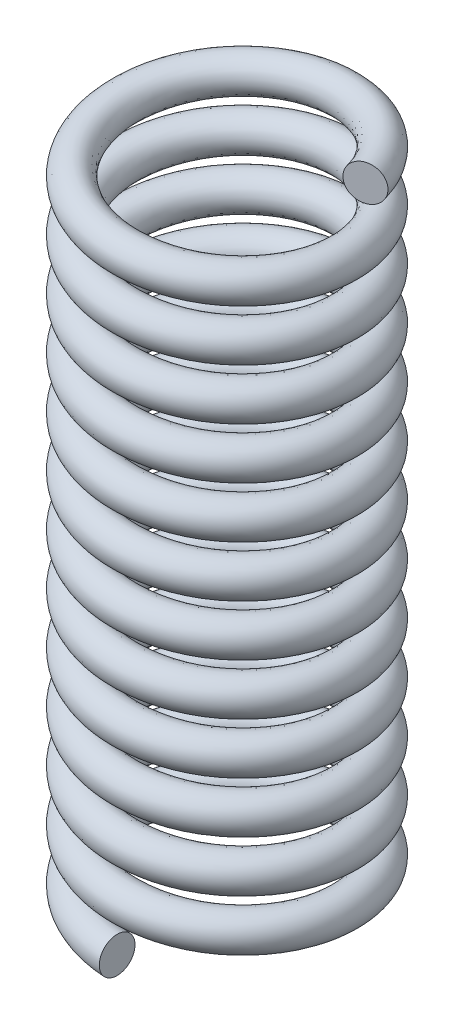
SolidWorks part; units mm, degrees
ref_plane "Front Plane" through (0, 0, 0) normal (0, 0, 1) x (1, 0, 0)
ref_plane "Top Plane" through (0, 0, 0) normal (0, 1, 0) x (1, 0, 0)
ref_plane "Right Plane" through (0, 0, 0) normal (1, 0, 0) x (0, 0, -1)
sketch "Sketch3" plane through (0, 0, 0) normal (0, 1, 0) x (1, 0, 0)
  circle A0 centre (0, 0) radius 2.15
  dimension "D1" = 4.3
curve "Helix/Spiral2" pitch 1 height 12.7 turns 12.7
sketch "Sketch4" plane through (0, 0, 0) normal (0, 0, 1) x (1, 0, 0)
  circle A0 centre (-2.15, 0.25) radius 0.35
  point P2 (0, 0)
sweep "Sweep2" add profiles "Sketch4" path "Helix/Spiral2"
